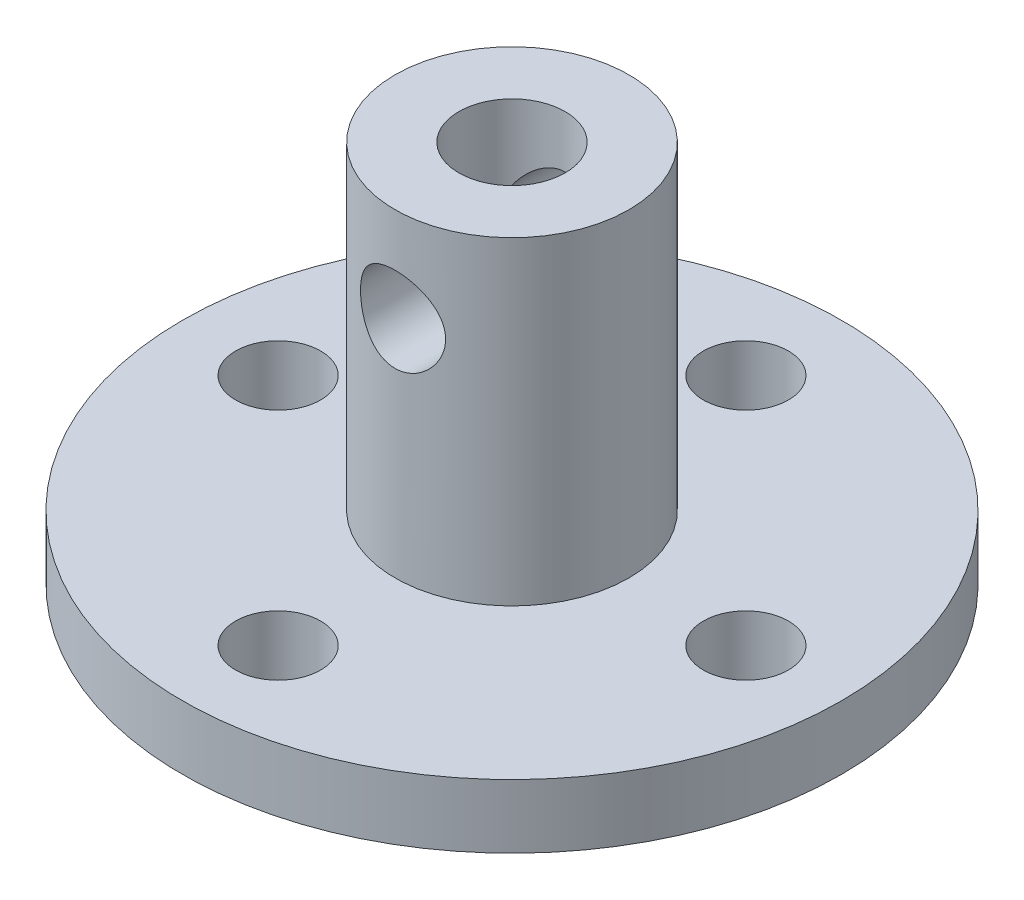
SolidWorks part; units mm, degrees
ref_plane "Front Plane" through (0, 0, 0) normal (0, 0, 1) x (1, 0, 0)
ref_plane "Top Plane" through (0, 0, 0) normal (0, 1, 0) x (1, 0, 0)
ref_plane "Right Plane" through (0, 0, 0) normal (1, 0, 0) x (0, 0, -1)
sketch "Sketch1" plane through (0, 0, 0) normal (0, 0, 1) x (1, 0, 0)
  line L0 (0, -76.9507) -> (0, 3770.5846) construction
  line L1 (-2.5, 0) -> (-2.5, -18)
  line L2 (-2.5, -18) -> (-15.5, -18)
  line L3 (-15.5, -18) -> (-15.5, -15)
  line L4 (-15.5, -15) -> (-5.5, -15)
  line L5 (-5.5, -15) -> (-5.5, 0)
  line L6 (-5.5, 0) -> (-2.5, 0)
  dimension "D1" = 2.5
  dimension "D2" = 18
  dimension "D3" = 3
  dimension "D4" = 3
  dimension "D5" = 10
revolve "Revolve1" add sketch "Sketch1" angle 360 about L0
sketch "Sketch2" plane through (0, 0, 0) normal (0, 0, 1) x (1, 0, 0)
  circle A0 centre (0, -4.4629) radius 2
  dimension "D1" = 4
extrude "Cut-Extrude1" cut sketch "Sketch2" against normal blind 10 and the other way blind 10
sketch "Sketch3" plane through (0, -15, 0) normal (0, 1, 0) x (1, 0, 0)
  line L0 (0, 15.5) -> (0, -15.5) construction
  line L1 (-15.5, 0) -> (15.5, 0) construction
  circle A0 centre (0, 0) radius 15.5 construction
  circle A1 centre (0, 0) radius 11 construction
  circle A2 centre (0, 11) radius 2
  circle A3 centre (11, 0) radius 2
  circle A4 centre (0, -11) radius 2
  circle A5 centre (-11, 0) radius 2
  dimension "D1" = 22
  dimension "D2" = 4
extrude "Cut-Extrude2" cut sketch "Sketch3" against normal blind 10
